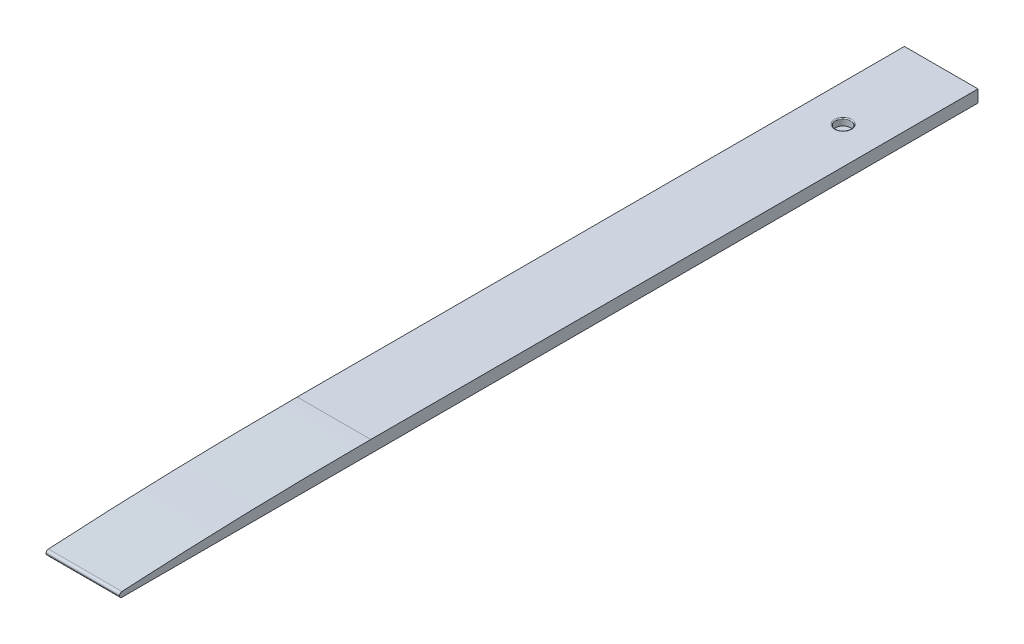
SolidWorks part; units mm, degrees
other "标注1"
sketch "草图6" plane through (0, 5, 350) normal (-0.6393, 0.5849, 0.4992) x (0.7619, 0.3939, 0.5141)
sketch "草图7" plane through (0, 5, 350) normal (-0.6393, 0.5849, 0.4992) x (0.7619, 0.3939, 0.5141)
sketch "草图8" plane through (0, 5, 350) normal (-0.6393, 0.5849, 0.4992) x (0.7619, 0.3939, 0.5141)
ref_plane "前视基准面" through (0, 0, 0) normal (0, 0, 1) x (1, 0, 0)
ref_plane "上视基准面" through (0, 0, 0) normal (0, 1, 0) x (1, 0, 0)
ref_plane "右视基准面" through (0, 0, 0) normal (1, 0, 0) x (0, 0, -1)
other "Configuration Table"
sketch "草图1" plane through (0, 0, 0) normal (1, 0, 0) x (0, 0, -1)
  line L0 (0, 0) -> (-350, 0)
  line L5 (0, 5) -> (0, 0)
  line L6 (-300, 5) -> (0, 5)
  line L7 (-350, 0) -> (-350, 2)
  line L8 (-350, 2) -> (-300, 5)
  dimension "D1" = 350
  dimension "D2" = 5
  dimension "D3" = 2
  dimension "D7" = 50
extrude "凸台-拉伸1" add sketch "草图1" along normal blind 30
fillet "圆角1" radius 1750 1 edges at (15, 5, 300)
sketch "草图4" plane through (0, 5, 0) normal (0, 1, 0) x (1, 0, 0)
  line L0 (15, 0) -> (15, -40) construction
  line L1 (30, 0) -> (0, 0) construction
  line L2 (15, 0) -> (15, -40) construction
  circle A0 centre (15, -40) radius 3.1
  dimension "D2" = 6.2
  dimension "D1" = 40
extrude "切除-拉伸3" cut sketch "草图4" against normal blind 2.8
fillet "圆角4" radius 0.4 1 edges at (15, 5, 43.1)
sketch "草图5" plane through (0, 0, 0) normal (0, 0, -1) x (-1, 0, 0)
  line L0 (0, 0) -> (0, 5) construction
  line L1 (-25, 3.5) -> (-5, 3.5)
  line L2 (-25, 3.5) -> (-25, 1.5)
  line L3 (-25, 1.5) -> (-5, 1.5)
  line L4 (-5, 3.5) -> (-5, 1.5)
  line L5 (-30, 0) -> (-30, 5) construction
  line L6 (-30, 5) -> (0, 5) construction
  line L7 (-30, 0) -> (0, 0) construction
  dimension "D1" = 5
  dimension "D2" = 5
  dimension "D3" = 1.5
  dimension "D4" = 1.5
extrude "切除-拉伸4" cut sketch "草图5" against normal blind 25
fillet "圆角5" radius 1 2 edges at (15, 0, 350) (15, 2, 350)
fillet "圆角6" radius 1 2 edges at (15, 1.5, 0) (15, 3.5, 0)
